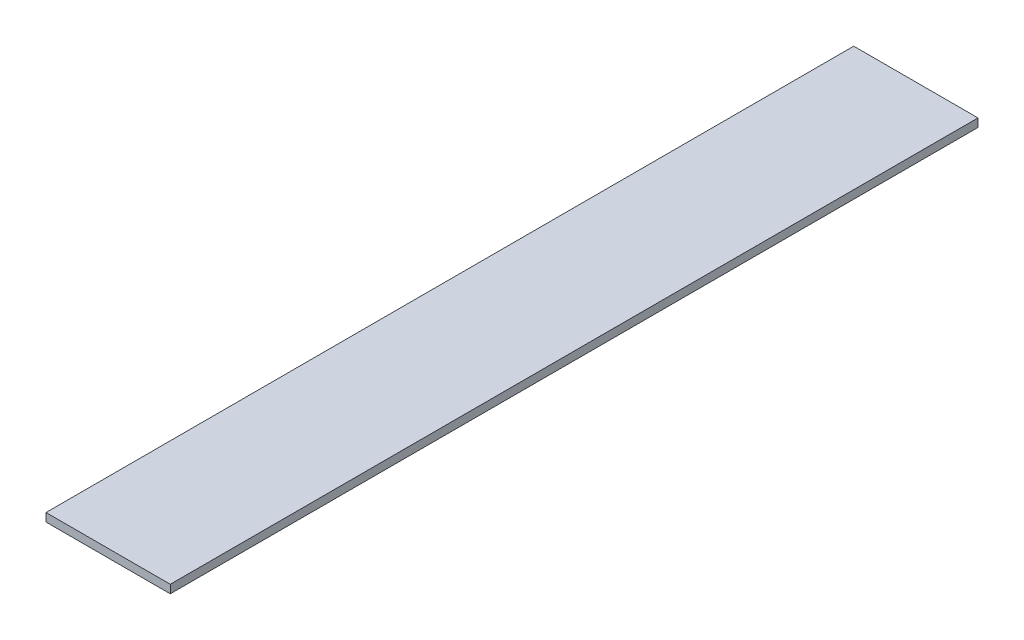
SolidWorks part; units mm, degrees
ref_plane "Front Plane" through (0, 0, 0) normal (0, 0, 1) x (1, 0, 0)
ref_plane "Top Plane" through (0, 0, 0) normal (0, 1, 0) x (1, 0, 0)
ref_plane "Right Plane" through (0, 0, 0) normal (1, 0, 0) x (0, 0, -1)
sketch "Sketch2" plane through (0, 0, 0) normal (0, 1, 0) x (1, 0, 0)
  line L1 (-125.4545, 349.7727) -> (-65.4545, 349.7727)
  line L2 (-125.4545, 349.7727) -> (-125.4545, -40.2273)
  line L3 (-125.4545, -40.2273) -> (-65.4545, -40.2273)
  line L4 (-65.4545, 349.7727) -> (-65.4545, -40.2273)
  line L5 (-125.4545, 349.7727) -> (-65.4545, -40.2273) construction
  line L6 (-125.4545, -40.2273) -> (-65.4545, 349.7727) construction
  point P0 (-95.4545, 154.7727)
  dimension "D1" = 390
  dimension "D2" = 60
extrude "Boss-Extrude1" add sketch "Sketch2" along normal blind 4
